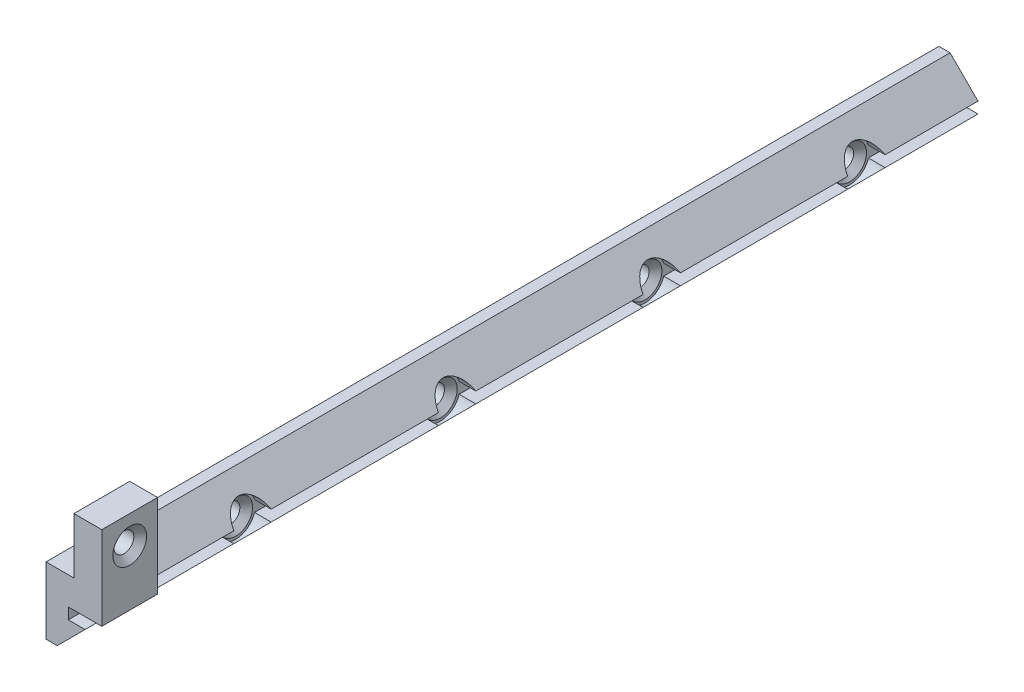
SolidWorks part; units mm, degrees
ref_plane "Front Plane" through (0, 0, 0) normal (0, 0, 1) x (1, 0, 0)
ref_plane "Top Plane" through (0, 0, 0) normal (0, 1, 0) x (1, 0, 0)
ref_plane "Right Plane" through (0, 0, 0) normal (1, 0, 0) x (0, 0, -1)
sketch "Sketch1" plane through (0, 0, 0) normal (0, 0, 1) x (1, 0, 0)
  line L0 (-2, 0) -> (0, 0) construction
  line L1 (-2, -3) -> (2, -3)
  line L2 (-2, -3) -> (-2, 3)
  line L3 (-2, 3) -> (2, 3)
  line L4 (2, -3) -> (2, -0.5)
  line L5 (-2, -3) -> (2, 3) construction
  line L6 (-2, 3) -> (2, -3) construction
  line L7 (2, 0.5) -> (0, 0.5)
  line L9 (2, -0.5) -> (0, -0.5)
  line L10 (0, 0.5) -> (0, -0.5)
  line L11 (2, 0.5) -> (2, 3)
  point P0 (0, 0)
  dimension "D1" = 1
  dimension "D2" = 6
  dimension "D3" = 2
  dimension "D4" = 4
extrude "Boss-Extrude1" add sketch "Sketch1" along normal blind 75
sketch "Sketch5" plane through (2, 0, 0) normal (1, 0, 0) x (0, 0, -1)
  line L1 (-75, 0) -> (0, 0) construction
  line L4 (-75, -0.5) -> (-75, 0.5) construction
  circle A0 centre (-65, 0) radius 1.75
  circle A1 centre (-46.6667, 0) radius 1.75
  circle A2 centre (-28.3333, 0) radius 1.75
  circle A3 centre (-10, 0) radius 1.75
  point P6 (-65, 0)
  dimension "D1" = 3.5
  dimension "D2" = 10
  dimension "D3" = 10
  dimension "D5" = 4
extrude "Cut-Extrude1" cut sketch "Sketch5" against normal up to surface (2 mm away) up to face at (0, 0, 37.5)
hole_wizard "CSK for #0 Flat Head Machine Screw (100)1" positions "Sketch4" profile "Sketch2" countersink size "#0" standard "ANSI Inch"
sketch "Sketch4" plane through (0, 0, 0) normal (1, 0, 0) x (0, 0, -1)
  arc A0 (-63.3229, 0.5) -> (-66.6771, 0.5) centre (-65, 0) ccw construction
  arc A3 (-44.9896, 0.5) -> (-48.3437, 0.5) centre (-46.6667, 0) ccw construction
  arc A4 (-8.323, 0.5) -> (-11.6771, 0.5) centre (-10, 0) ccw construction
  point P0 (-65, 0)
  point P2 (-10, 0)
  point P4 (-46.6667, 0)
  point P25 (-28.3333, 0)
sketch "Sketch2" plane through (0, 0, 65) normal (0, 1, 0) x (0, 0, -1)
  line L0 (0, 0) -> (0, 3.8362)
  line L1 (0, 3.8362) -> (0.889, 3.302)
  line L2 (0.889, 3.302) -> (0.889, 0.5222)
  line L3 (0.889, 0.5222) -> (1.5113, 0)
  line L5 (1.5113, 0) -> (0, 0)
  line L6 (-0.889, 0.5222) -> (-1.5113, 0) construction
  line L10 (0, 3.8362) -> (-0.889, 3.302) construction
  line L11 (0, -6.35) -> (0, 107.95) construction
  dimension "Hole Dia." = 1.778
  dimension "Hole Depth" = 3.302
  dimension "Near C'Sink Dia." = 3.0226
  dimension "Near C'Sink Angle" = 100
  dimension "Drill Angle" = 118
chamfer "Chamfer1" distance 3 angle 45 2 edges at (2, -3, 37.5) (2, 3, 37.5)
sketch "Sketch6" plane through (0, 0, 75) normal (0, 0, 1) x (1, 0, 0)
  line L0 (-2, -3) -> (-1, -3) construction
  line L1 (0.5, 8) -> (3, 8)
  line L2 (-2, 3) -> (-2, -3)
  line L3 (-2, -3) -> (2, -3)
  line L4 (3, 8) -> (3, 0.5)
  line L5 (-2, 3) -> (-2, -3) construction
  line L6 (2, -0.5) -> (2, -3)
  line L7 (3, 0.5) -> (0, 0.5)
  line L8 (0, 0.5) -> (1.5, 0.5) construction
  line L9 (2, -0.5) -> (0, -0.5)
  line L10 (0, 0.5) -> (0, -0.5)
  line L11 (-2, 3) -> (0.5, 3)
  line L12 (-1, 3) -> (-2, 3) construction
  line L13 (0.5, 3) -> (0.5, 8)
  dimension "D1" = 5
  dimension "D2" = 4
  dimension "D3" = 5
  dimension "D4" = 2.5
extrude "Boss-Extrude2" add sketch "Sketch6" along normal blind 5
chamfer "Chamfer2" distance 3 angle 45 1 edges at (2, -3, 77.5)
hole_wizard "CSK for #0 Flat Head Machine Screw (100)2" positions "Sketch8" profile "Sketch7" countersink size "#0" standard "ANSI Inch"
sketch "Sketch8" plane through (3, 0, 0) normal (1, 0, 0) x (0, 0, -1)
  line L1 (-80, 3) -> (-75, 3) construction
  line L2 (-80, 3) -> (-80, 8) construction
  line L3 (-80, 8) -> (-75, 8) construction
  line L4 (-75, 3) -> (-75, 8) construction
  line L5 (-80, 3) -> (-75, 8) construction
  line L6 (-80, 8) -> (-75, 3) construction
  line L7 (-80, 0.5) -> (-80, 8) construction
  point P0 (-77.5, 5.5)
  point P4 (-77.5, 5.5)
  dimension "D1" = 5
sketch "Sketch7" plane through (3, 5.5, 77.5) normal (0, 1, 0) x (0, 0, -1)
  line L0 (0, 0) -> (0, 3.8362)
  line L1 (0, 3.8362) -> (0.889, 3.302)
  line L2 (0.889, 3.302) -> (0.889, 0.5222)
  line L3 (0.889, 0.5222) -> (1.5113, 0)
  line L5 (1.5113, 0) -> (0, 0)
  line L6 (-0.889, 0.5222) -> (-1.5113, 0) construction
  line L10 (0, 3.8362) -> (-0.889, 3.302) construction
  line L11 (0, -6.35) -> (0, 107.95) construction
  dimension "Hole Dia." = 1.778
  dimension "Hole Depth" = 3.302
  dimension "Near C'Sink Dia." = 3.0226
  dimension "Near C'Sink Angle" = 100
  dimension "Drill Angle" = 118
